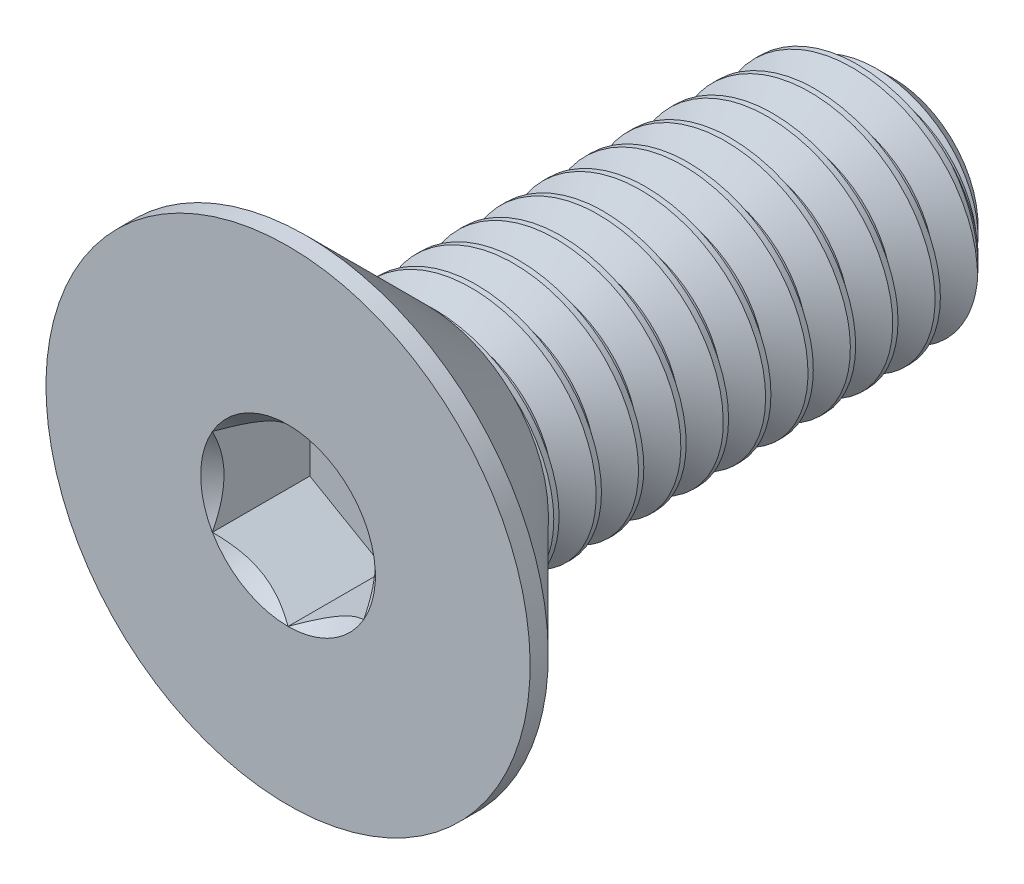
SolidWorks part; units mm, degrees
ref_plane "Front" through (0, 0, 0) normal (0, 0, 1) x (1, 0, 0)
ref_plane "Top" through (0, 0, 0) normal (0, 1, 0) x (1, 0, 0)
ref_plane "Right" through (0, 0, 0) normal (1, 0, 0) x (0, 0, -1)
sketch "Sketch1" plane through (0, 0, 0) normal (1, 0, 0) x (0, 0, -1)
  line L0 (-5, 4) -> (-4.7, 4) construction
  line L1 (-4.7, 4) -> (-2.7, 2) construction
  line L2 (-5, 2) -> (5, 2) construction
  line L3 (5, 2) -> (5, 0) construction
  line L4 (5, 0) -> (-5, 0) construction
  line L5 (-5, 0) -> (-5, 4) construction
  line L6 (-5, 4) -> (-5, -4) construction
  line L7 (5, 2) -> (5, -2) construction
  line L8 (-5, -4) -> (-4.7, -4) construction
  line L9 (-4.7, -4) -> (-2.7, -2) construction
  line L11 (-5, 2) -> (-5, 0) construction
  line L12 (-2.7, 2) -> (-2.7, 0) construction
  line L13 (4.9563, 2.0758) -> (5.3063, 1.4696) construction
  line L14 (5.3063, 1.4696) -> (5.6563, 2.0758) construction
  line L15 (5.6563, 2.0758) -> (4.9563, 2.0758) construction
  line L16 (5.3063, 2.0758) -> (5.3063, 2) construction
  line L17 (5.3063, 2) -> (5.3063, 1.5453) construction
  line L18 (5.3063, 1.5453) -> (5.3063, 1.4696) construction
  line L19 (5.3063, 2.0379) -> (5.6344, 2.0379) construction
  line L20 (5.3063, 2.0379) -> (4.9781, 2.0379) construction
  line L21 (5, 2) -> (5.6125, 2) construction
  line L22 (5.2625, 1.5453) -> (5.35, 1.5453) construction
  line L23 (5, -2) -> (-2.7, -2) construction
  point P10 (3.25, -2)
  point P24 (-2.7, 2)
  point P30 (0, 0)
  dimension "Head Diameter" = 8
  dimension "Head Height" = 2.3
  dimension "Length" = 10
  dimension "Countersink Angle" = 90
  dimension "Thread Pitch" = 0.7
  dimension "D2" = 0.0875
  dimension "Thread Size" = 4
  dimension "D1" = 1.75
sketch "Sketch2" plane through (0, 0, 0) normal (0, 0, 1) x (1, 0, 0)
  line L1 (0, 1.4434) -> (-1.25, 0.7217) construction
  line L2 (-1.25, 0.7217) -> (-1.25, -0.7217) construction
  line L3 (-1.25, -0.7217) -> (0, -1.4434) construction
  line L4 (0, -1.4434) -> (1.25, -0.7217) construction
  line L5 (1.25, -0.7217) -> (1.25, 0.7217) construction
  line L6 (1.25, 0.7217) -> (0, 1.4434) construction
  circle A0 centre (0, 0) radius 1.25 construction
  dimension "Drive Size" = 2.5
sketch "Sketch3" plane through (0, 0, 0) normal (1, 0, 0) x (0, 0, -1)
  line L0 (-5, 2) -> (5, 2)
  line L1 (5, 2) -> (5, 0)
  line L2 (5, 0) -> (-5, 0)
  line L3 (-5, 0) -> (-5, 2)
revolve "Revolve1" add sketch "Sketch3" angle 360 about L4
chamfer "Chamfer1" distance 0.6 angle 45 1 edges at (0, 2, -5)
sketch "Sketch6" plane through (0, 0, 0) normal (1, 0, 0) x (0, 0, -1)
  line L0 (-5, 4) -> (-4.7, 4)
  line L1 (-4.7, 4) -> (-2.7, 2)
  line L2 (-2.7, 2) -> (-2.7, 0)
  line L3 (-2.7, 0) -> (-5, 0)
  line L4 (-5, 0) -> (-5, 4)
revolve "Revolve2" add sketch "Sketch6" angle 360 about L4
sketch "Sketch8" plane through (0, 0, 5) normal (0, 0, 1) x (1, 0, 0)
  line L0 (0, 1.4434) -> (-1.25, 0.7217) construction
  line L1 (1.25, 0.7217) -> (0, 1.4434) construction
  line L2 (1.25, -0.7217) -> (1.25, 0.7217) construction
  line L3 (0, -1.4434) -> (1.25, -0.7217) construction
  line L4 (-1.25, 0.7217) -> (-1.25, -0.7217) construction
  line L5 (-1.25, -0.7217) -> (0, -1.4434) construction
  line L6 (0, 1.4434) -> (-1.25, 0.7217)
  line L7 (1.25, 0.7217) -> (0, 1.4434)
  line L8 (1.25, -0.7217) -> (1.25, 0.7217)
  line L9 (0, -1.4434) -> (1.25, -0.7217)
  line L10 (-1.25, 0.7217) -> (-1.25, -0.7217)
  line L11 (-1.25, -0.7217) -> (0, -1.4434)
extrude "Cut-Extrude1" cut sketch "Sketch8" against normal blind 1.61
sketch "Sketch9" plane through (0, 0, 5) normal (0, 0, 1) x (1, 0, 0)
  circle A0 centre (0, 0) radius 1.4434
extrude "Cut-Extrude2" cut sketch "Sketch9" against normal up to next (1.61 mm away) draft 45
ref_plane "Plane1" through (0, 0, 2.7) normal (0, 0, 1) x (1, 0, 0)
split "Split1" trim tools "Plane1" bodies to split 124 resulting bodies 126 127
sketch "Sketch4" plane through (0, 0, -5) normal (0, 0, -1) x (-1, 0, 0)
  circle A0 centre (0, 0) radius 2 construction
  circle A1 centre (0, 0) radius 2
curve "Helix/Spiral1" pitch 0.7 height 10 radius 2 centre (0, 0, -5) axis (0, 0, 1) start towards (0, 1, 0)
sketch "Sketch10" plane through (0, 0, 0) normal (1, 0, 0) x (0, 0, -1)
  line L0 (4.9781, 2.0379) -> (5.6344, 2.0379)
  line L1 (5.6344, 2.0379) -> (5.35, 1.5453)
  line L2 (5.35, 1.5453) -> (5.2625, 1.5453)
  line L3 (5.2625, 1.5453) -> (4.9781, 2.0379)
sweep "Cut-Sweep1" cut profiles "Sketch10" path "Helix/Spiral1" align with end faces yes
combine bodies "Combine1" operation type add bodies to combine 130 126
equation "\"D2@Sketch1\" = \"Thread Pitch@Sketch1\" / 8"
equation "\"D4@Helix/Spiral1\"=\"Thread Pitch@Sketch1\""
equation "\"D1@Chamfer1\"=\"Thread Size@Sketch1\"*.15"
equation "\"D1@Cut-Extrude1\"=\"Head Height@Sketch1\"*.7"
equation "\"D1@Sketch1\"=\"Thread Pitch@Sketch1\"*2.5"
equation "\"D3@Helix/Spiral1\"=\"Length@Sketch1\""
